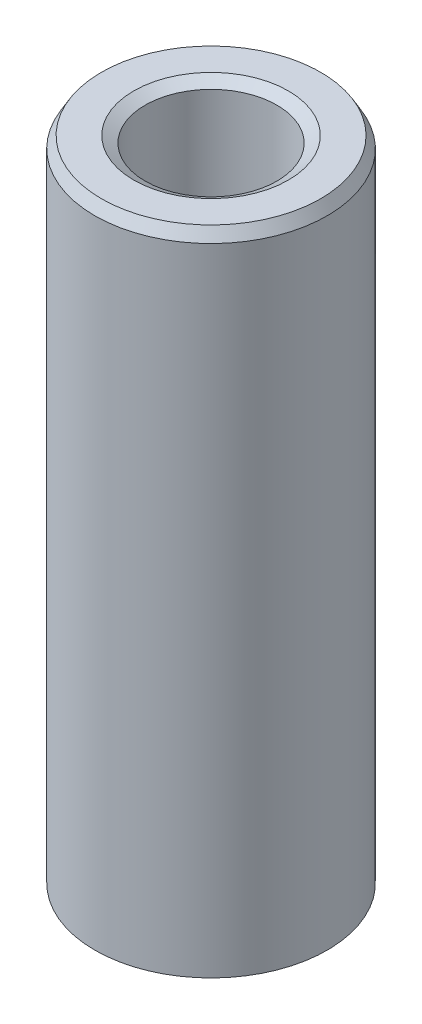
SolidWorks part; units mm, degrees
ref_plane "Front Plane" through (0, 0, 0) normal (0, 0, 1) x (1, 0, 0)
ref_plane "Top Plane" through (0, 0, 0) normal (0, 1, 0) x (1, 0, 0)
ref_plane "Right Plane" through (0, 0, 0) normal (1, 0, 0) x (0, 0, -1)
sketch "Sketch1" plane through (0, 0, 0) normal (0, 1, 0) x (1, 0, 0)
  circle A0 centre (0, 0) radius 25
  dimension "SLEEVE_OD" = 50
extrude "Boss-Extrude1" add sketch "Sketch1" along normal blind 140.7111
sketch "Sketch2" plane through (0, 0, 0) normal (0, 1, 0) x (1, 0, 0)
  circle A0 centre (0, 0) radius 14.1718
  dimension "BORE_D" = 28.3436
extrude "Cut-Extrude1" cut sketch "Sketch2" along normal through all
chamfer "Chamfer1" distance 2.4597 angle 30 4 edges at (0, 140.7111, 14.1718) (0, 0, 14.1718) (0, 0, 25) (0, 140.7111, 25) first distance on face at (0, 140.7111, 14.1718) first distance on face at (0, 0, 14.1718) first distance on face at (0, 140.7111, 25)
